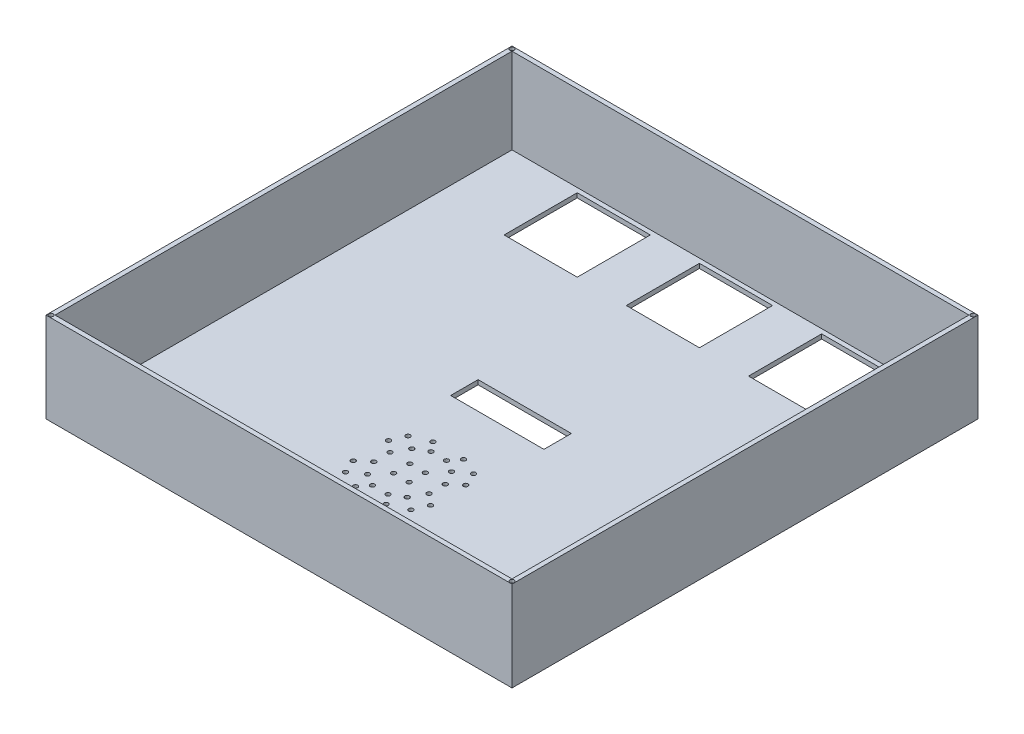
SolidWorks part; units mm, degrees
ref_plane "Front Plane" through (0, 0, 0) normal (0, 0, 1) x (1, 0, 0)
ref_plane "Top Plane" through (0, 0, 0) normal (0, 1, 0) x (1, 0, 0)
ref_plane "Right Plane" through (0, 0, 0) normal (1, 0, 0) x (0, 0, -1)
sketch "Sketch1" plane through (0, 0, 0) normal (0, 1, 0) x (1, 0, 0)
  line L0 (0, 0) -> (50.8, 0)
  line L17 (50.8, 0) -> (50.8, 50.8)
  line L18 (50.8, 50.8) -> (0, 50.8)
  line L19 (0, 50.8) -> (0, 0)
  line L21 (7.75, 50.3) -> (15.878, 50.3)
  line L22 (7.75, 50.3) -> (7.75, 42.172)
  line L23 (7.75, 42.172) -> (15.878, 42.172)
  line L24 (15.878, 50.3) -> (15.878, 42.172)
  line L25 (21.334, 50.3) -> (29.464, 50.3)
  line L26 (21.334, 50.3) -> (21.334, 42.17)
  line L27 (21.334, 42.17) -> (29.464, 42.17)
  line L28 (29.464, 50.3) -> (29.464, 42.17)
  line L29 (34.92, 50.3) -> (43.05, 50.3)
  line L30 (34.92, 50.3) -> (34.92, 42.17)
  line L31 (34.92, 42.17) -> (43.05, 42.17)
  line L32 (43.05, 50.3) -> (43.05, 42.17)
  line L33 (20.232, 26.8) -> (30.6, 26.8)
  line L34 (20.232, 26.8) -> (20.232, 23.75)
  line L35 (20.232, 23.75) -> (30.6, 23.75)
  line L36 (30.6, 26.8) -> (30.6, 23.75)
  line L37 (51.3, 51.3) -> (-0.5, 51.3)
  line L38 (51.3, 51.3) -> (51.3, -0.5)
  line L39 (51.3, -0.5) -> (-0.5, -0.5)
  line L40 (-0.5, 51.3) -> (-0.5, -0.5)
  circle A2 centre (25.4, 14.0043) radius 6.035
  circle A3 centre (21.7655, 17.4813) radius 0.25
  circle A5 centre (23.7008, 18.308) radius 0.25
  circle A6 centre (21.1079, 15.9593) radius 0.25
  circle A7 centre (23.1935, 16.4666) radius 0.25
  circle A8 centre (24.5366, 14.9071) radius 0.25
  circle A9 centre (22.3292, 14.9071) radius 0.25
  circle A10 centre (24.5366, 17.2542) radius 0.25
  circle A11 centre (26.2634, 14.9071) radius 0.25
  circle A12 centre (28.4708, 14.9071) radius 0.25
  circle A13 centre (29.6921, 15.9593) radius 0.25
  circle A14 centre (27.6065, 16.4666) radius 0.25
  circle A15 centre (26.2634, 17.2542) radius 0.25
  circle A16 centre (29.0345, 17.4813) radius 0.25
  circle A17 centre (27.0992, 18.308) radius 0.25
  circle A18 centre (24.5366, 13.1015) radius 0.25
  circle A19 centre (22.3292, 13.1015) radius 0.25
  circle A20 centre (29.0345, 10.5274) radius 0.25
  circle A21 centre (27.0992, 9.7006) radius 0.25
  circle A22 centre (26.2634, 10.7544) radius 0.25
  circle A23 centre (27.6065, 11.542) radius 0.25
  circle A24 centre (29.6921, 12.0493) radius 0.25
  circle A25 centre (28.4708, 13.1015) radius 0.25
  circle A26 centre (26.2634, 13.1015) radius 0.25
  circle A27 centre (24.5366, 10.7544) radius 0.25
  circle A28 centre (23.1935, 11.542) radius 0.25
  circle A29 centre (21.1079, 12.0493) radius 0.25
  circle A30 centre (23.7008, 9.7006) radius 0.25
  circle A31 centre (21.7655, 10.5274) radius 0.25
  point P23 (25.4, 0)
  point P27 (25.4, 14.0043)
  point P30 (25.4, 14.0043)
  point P86 (25.4, 51.3)
  point P87 (25.4, 50.8)
  point P88 (51.3, 25.4)
  point P89 (50.8, 25.4)
  dimension "D3" = 12.07
  dimension "D4" = 0.5
  dimension "D6" = 0.5
  dimension "D5" = 0.5
  dimension "D7" = 0.5
  dimension "D8" = 0.5
  dimension "D9" = 0.5
  dimension "D10" = 0.5
  dimension "D1" = 50.8
  dimension "D2" = 50.8
  dimension "D11" = 3.05
  dimension "D12" = 24
  dimension "D13" = 7.75
  dimension "D14" = 7.75
  dimension "D15" = 8.128
  dimension "D16" = 8.128
  dimension "D17" = 8.13
  dimension "D18" = 8.13
  dimension "D19" = 0.5
  dimension "D20" = 0.5
  dimension "D21" = 8.13
  dimension "D22" = 8.13
  dimension "D23" = 0.5
  dimension "D24" = 10.368
  dimension "D25" = 20.2
  dimension "D26" = 51.8
  dimension "D27" = 51.8
ref_plane "Plane1" through (0, 10, 0) normal (0, 1, 0) x (1, 0, 0)
sketch "Sketch2" plane through (0, 10, 0) normal (0, 1, 0) x (1, 0, 0)
  line L1 (2.5766, 58.5763) -> (54.3766, 58.5763)
  line L2 (2.5766, 58.5763) -> (2.5766, 6.7763)
  line L3 (2.5766, 6.7763) -> (54.3766, 6.7763)
  line L4 (54.3766, 58.5763) -> (54.3766, 6.7763)
  dimension "D1" = 51.8
  dimension "D2" = 51.8
extrude "Boss-Extrude1" add sketch "Sketch2" along normal blind 20
sketch "Sketch3" plane through (0, 30, 0) normal (0, 1, 0) x (1, 0, 0)
  line L0 (54.3766, 58.5763) -> (2.5766, 58.5763) construction
  line L1 (3.0766, 58.0763) -> (53.8766, 58.0763)
  line L2 (3.0766, 58.0763) -> (3.0766, 7.2763)
  line L3 (3.0766, 7.2763) -> (53.8766, 7.2763)
  line L4 (53.8766, 58.0763) -> (53.8766, 7.2763)
  line L7 (2.5766, 58.5763) -> (2.5766, 6.7763) construction
  dimension "D1" = 50.8
  dimension "D2" = 50.8
  dimension "D3" = 0.5
  dimension "D4" = 0.5
extrude "Cut-Extrude1" cut sketch "Sketch3" against normal blind 19.5
sketch "Sketch4" plane through (0, 10, 0) normal (0, -1, 0) x (1, 0, 0)
  line L4 (2.5766, -6.7763) -> (2.5766, -58.5763)
  line L5 (2.5766, -58.5763) -> (54.3766, -58.5763)
  line L6 (54.3766, -58.5763) -> (54.3766, -6.7763)
  line L7 (54.3766, -6.7763) -> (2.5766, -6.7763)
  line L9 (2.5766, -58.5763) -> (54.3766, -58.5763)
  line L10 (54.3766, -58.5763) -> (54.3766, -6.7763)
  line L16 (24.4106, -57.5763) -> (32.5406, -57.5763)
  line L17 (32.5406, -57.5763) -> (32.5406, -49.4463)
  line L18 (32.5406, -49.4463) -> (24.4106, -49.4463)
  line L19 (24.4106, -49.4463) -> (24.4106, -57.5763)
  line L24 (10.8266, -57.5763) -> (18.9546, -57.5763)
  line L25 (18.9546, -57.5763) -> (18.9546, -49.4483)
  line L26 (18.9546, -49.4483) -> (10.8266, -49.4483)
  line L27 (10.8266, -49.4483) -> (10.8266, -57.5763)
  line L32 (53.8766, -7.2763) -> (3.0766, -7.2763)
  line L33 (53.8766, -58.0763) -> (53.8766, -7.2763)
  line L34 (3.0766, -58.0763) -> (53.8766, -58.0763)
  line L35 (3.0766, -7.2763) -> (3.0766, -58.0763)
  line L40 (2.5766, -58.5763) -> (54.3766, -58.5763)
  line L41 (2.5766, -6.7763) -> (2.5766, -58.5763)
  line L42 (54.3766, -6.7763) -> (2.5766, -6.7763)
  line L43 (54.3766, -58.5763) -> (54.3766, -6.7763)
  line L48 (23.3086, -34.0763) -> (33.6766, -34.0763)
  line L49 (33.6766, -34.0763) -> (33.6766, -31.0263)
  line L50 (33.6766, -31.0263) -> (23.3086, -31.0263)
  line L51 (23.3086, -31.0263) -> (23.3086, -34.0763)
  line L56 (37.9966, -57.5763) -> (46.1266, -57.5763)
  line L57 (37.9966, -49.4463) -> (37.9966, -57.5763)
  line L58 (46.1266, -49.4463) -> (37.9966, -49.4463)
  line L59 (46.1266, -57.5763) -> (46.1266, -49.4463)
  circle A2 centre (24.8422, -24.7576) radius 0.25
  circle A4 centre (28.4766, -21.2806) radius 6.035
  circle A6 centre (31.5474, -22.1834) radius 0.25
  circle A8 centre (29.34, -22.1834) radius 0.25
  circle A10 centre (27.6132, -24.5305) radius 0.25
  circle A12 centre (25.4058, -22.1834) radius 0.25
  circle A14 centre (27.6132, -22.1834) radius 0.25
  circle A16 centre (26.2701, -23.7429) radius 0.25
  circle A18 centre (24.1845, -23.2356) radius 0.25
  circle A20 centre (26.7775, -25.5843) radius 0.25
  circle A22 centre (32.1111, -17.8037) radius 0.25
  circle A24 centre (25.4058, -20.3778) radius 0.25
  circle A26 centre (27.6132, -20.3778) radius 0.25
  circle A28 centre (30.1758, -25.5843) radius 0.25
  circle A30 centre (32.1111, -24.7576) radius 0.25
  circle A32 centre (29.34, -24.5305) radius 0.25
  circle A34 centre (30.6831, -23.7429) radius 0.25
  circle A36 centre (32.7687, -23.2356) radius 0.25
  circle A38 centre (26.2701, -18.8183) radius 0.25
  circle A40 centre (27.6132, -18.0307) radius 0.25
  circle A42 centre (29.34, -20.3778) radius 0.25
  circle A44 centre (31.5474, -20.3778) radius 0.25
  circle A46 centre (32.7687, -19.3256) radius 0.25
  circle A48 centre (30.6831, -18.8183) radius 0.25
  circle A50 centre (29.34, -18.0307) radius 0.25
  circle A52 centre (30.1758, -16.9769) radius 0.25
  circle A54 centre (24.8422, -17.8037) radius 0.25
  circle A56 centre (26.7775, -16.9769) radius 0.25
  circle A58 centre (24.1845, -19.3256) radius 0.25
  dimension "D1" = 0
extrude "Cut-Extrude2" cut sketch "Sketch4" against normal through all contours L56 L59 L58 L57 | L18 L19 L16 L17 | L26 L27 L24 L25 | L50 L51 L48 L49 | A36 | A30 | A28 | A34 | A32 | A10 | A20 | A42 | A44 | A6 | A16 | A2 | A18 | A12 | A24 | A14 | A8 | A48 | A22 | A50 | A52 | A56 | A40 | A38 | A54 | A58 region at (28.4756, 10, -53.5113) region at (14.8906, 10, -53.5123) region at (28.4926, 10, -32.5513) region at (42.0616, 10, -53.5113) region at (24.8422, 10, -24.7576) region at (31.5474, 10, -22.1834) region at (27.6132, 10, -24.5305) region at (25.4058, 10, -22.1834) region at (26.2701, 10, -23.7429) region at (24.1845, 10, -23.2356) region at (26.7775, 10, -25.5843) region at (25.4058, 10, -20.3778) region at (30.1758, 10, -25.5843) region at (32.1111, 10, -24.7576) region at (29.34, 10, -24.5305) region at (30.6831, 10, -23.7429) region at (32.7687, 10, -23.2356) region at (29.34, 10, -20.3778) region at (31.5474, 10, -20.3778)
extrude "Cut-Extrude3" cut sketch "Sketch4<3>" against normal blind 19.5 contours A46 | A26 region at (27.6132, 10, -20.3778) region at (32.7687, 10, -19.3256)
sketch "Sketch4<3>" plane through (0, 10, 0) normal (0, -1, 0) x (1, 0, 0) same geometry as "Sketch4"
sketch "Sketch5" plane through (0, 0, -58.5763) normal (0, 0, -1) x (-1, 0, 0)
  line L0 (-54.3766, 20) -> (-2.5766, 20)
  line L1 (-54.3766, 30) -> (-54.3766, 10) construction
  line L2 (-2.5766, 30) -> (-2.5766, 10) construction
  line L3 (-2.5766, 20) -> (-2.5766, 30)
  line L4 (-2.5766, 30) -> (-54.3766, 30)
  line L5 (-54.3766, 30) -> (-54.3766, 20)
extrude "Cut-Extrude4" cut sketch "Sketch5" against normal through all
sketch "Sketch6" plane through (0, 20, 0) normal (0, 1, 0) x (1, 0, 0)
  line L0 (2.5766, 6.7763) -> (2.5766, 58.5763) construction
  line L1 (54.3766, 58.5763) -> (2.5766, 58.5763) construction
  circle A0 centre (2.853, 58.2999) radius 0.25
  circle A1 centre (54.1003, 58.2999) radius 0.25
  circle A2 centre (54.1003, 7.0527) radius 0.25
  circle A3 centre (2.853, 7.0527) radius 0.25
  point P10 (28.4766, 58.5763)
  point P11 (2.5766, 32.6763)
  point P16 (2.8557, 58.2972)
  point P19 (2.853, 58.2999)
  dimension "D1" = 0.5
extrude "Cut-Extrude8" cut sketch "Sketch6" against normal blind 2
